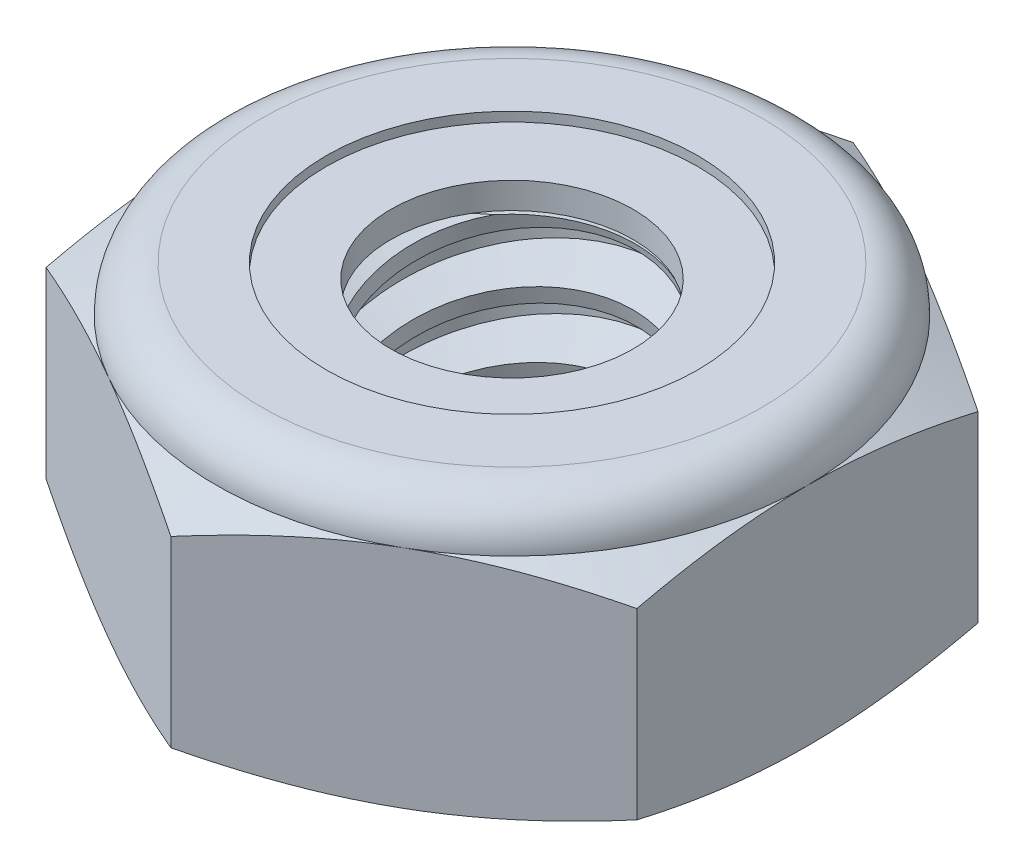
SolidWorks part; units mm, degrees
ref_plane "Front" through (0, 0, 0) normal (0, 0, 1) x (1, 0, 0)
ref_plane "Top" through (0, 0, 0) normal (0, 1, 0) x (1, 0, 0)
ref_plane "Right" through (0, 0, 0) normal (1, 0, 0) x (0, 0, -1)
sketch "Sketch1" plane through (0, 0, 0) normal (0, 1, 0) x (1, 0, 0)
  line L1 (0, 5.4993) -> (-4.7625, 2.7496)
  line L2 (-4.7625, 2.7496) -> (-4.7625, -2.7496)
  line L3 (-4.7625, -2.7496) -> (0, -5.4993)
  line L4 (0, -5.4993) -> (4.7625, -2.7496)
  line L5 (4.7625, -2.7496) -> (4.7625, 2.7496)
  line L6 (4.7625, 2.7496) -> (0, 5.4993)
  circle A0 centre (0, 0) radius 4.7625 construction
  dimension "Hex Flats" = 9.525
extrude "Extrude1" add sketch "Sketch1" along normal blind 4.3656
sketch "Sketch2" plane through (0, 0, 0) normal (1, 0, 0) x (0, 0, -1)
  line L0 (-2.413, 0) -> (-2.413, 4.3656) construction
  line L1 (0, 0) -> (2.413, 0)
  line L2 (0, 0) -> (0, 4.3656)
  line L3 (0, 4.3656) -> (2.413, 4.3656)
  line L4 (2.413, 0) -> (2.413, 4.3656)
  line L5 (-2.7496, 4.3656) -> (2.7496, 4.3656) construction
  line L7 (0, -2.413) -> (0, 0) construction
  dimension "Thread Dia" = 4.826
revolve "Revolve1" add sketch "Sketch2" angle 360 about L7
sketch "Sketch3" plane through (0, 0, 0) normal (1, 0, 0) x (0, 0, -1)
  line L0 (2.413, 4.3656) -> (-2.413, 4.3656) construction
  line L1 (-2.413, 4.3656) -> (-2.413, 3.3073) construction
  line L2 (-2.413, 3.3073) -> (2.413, 4.3656) construction
  line L3 (2.413, 4.3656) -> (2.4413, 4.2364) construction
  line L4 (2.4413, 4.2364) -> (2.6397, 3.3319)
  line L5 (2.6397, 3.3319) -> (2.0093, 3.5322)
  line L6 (2.0093, 3.5322) -> (1.9526, 3.7906)
  line L7 (1.9526, 3.7906) -> (2.4413, 4.2364)
  line L8 (1.981, 3.6614) -> (2.5405, 3.7841) construction
  line L9 (2.413, 4.3656) -> (2.413, 3.7562) construction
  line L10 (2.413, 3.7562) -> (-2.413, 2.6978) construction
  line L11 (-2.413, 2.6978) -> (-2.413, 3.3073) construction
  line L12 (-0.2497, 4.3656) -> (0.2497, 2.0884) construction
  line L13 (-2.413, 0) -> (-2.413, 4.3656) construction
  line L14 (0, 4.3656) -> (2.413, 4.3656) construction
  line L15 (2.413, 0) -> (2.413, 4.3656) construction
  point P13 (0, 3.227)
  dimension "D1" = 0.1323
  dimension "D2" = 0.2646
  dimension "Thread Pitch" = 1.0583
  dimension "D4" = 60
  dimension "D5" = 1.0583
revolve "Cut-Revolve1" cut sketch "Sketch3" angle 360 about L12
pattern_linear "LPattern1" count 4 spacing 1.0583 along (0, -1, 0) count 2 spacing 1.0583 along (0, 1, 0) of "Cut-Revolve1"
sketch "Sketch4" plane through (0, 0, 0) normal (1, 0, 0) x (0, 0, -1)
  line L0 (0, 4.3656) -> (2.413, 4.3656)
  line L1 (2.413, 4.3656) -> (1.9526, 4.151)
  line L2 (1.9526, 4.151) -> (1.9526, 0.2147)
  line L3 (1.9526, 0.2147) -> (2.413, 0)
  line L4 (2.413, 0) -> (0, 0)
  line L5 (0, 0) -> (0, 4.3656)
  line L6 (2.413, 0) -> (2.413, 4.3656) construction
  line L7 (0, 4.3656) -> (2.413, 4.3656) construction
  line L8 (0, 0) -> (2.413, 0) construction
  line L9 (0, 0) -> (0, 4.3656) construction
  line L10 (0, 4.3656) -> (0, 4.8736) construction
  dimension "D1" = 25
revolve "Cut-Revolve2" cut sketch "Sketch4" angle 360 about L10
combine bodies "Combine1" operation type subtract main body 112 bodies to subtract 111
sketch "Sketch5" plane through (0, 0, 0) normal (1, 0, 0) x (0, 0, -1)
  line L0 (0, 0) -> (4.7625, 0)
  line L1 (4.7625, 0) -> (5.4993, 0.3436)
  line L2 (5.4993, 0.3436) -> (5.4993, 3.2945)
  line L3 (5.4993, 3.2945) -> (4.7625, 3.638)
  line L4 (4.0349, 4.3656) -> (4.0349, 5.6356)
  line L5 (4.0349, 5.6356) -> (6.7693, 5.6356)
  line L6 (6.7693, 5.6356) -> (6.7693, -1.27)
  line L7 (6.7693, -1.27) -> (0, -1.27)
  line L8 (0, -1.27) -> (0, 0)
  line L9 (4.7625, 3.638) -> (4.7625, 0) construction
  line L10 (0, 0) -> (2.413, 0) construction
  line L13 (5.4993, 1.819) -> (6.7693, 1.819) construction
  line L14 (5.4993, 4.3656) -> (5.4993, 0) construction
  line L15 (0, 0) -> (0, 5.6356) construction
  line L20 (0, 5.6356) -> (4.0349, 5.6356) construction
  line L22 (0, 4.3656) -> (2.413, 4.3656) construction
  arc A0 (4.7625, 3.638) -> (4.0349, 4.3656) centre (4.0349, 3.638) ccw
  dimension "D1" = 25
  dimension "D2" = 1.27
  dimension "D3" = 4.3656
  dimension "D4" = 0.7276
revolve "Cut-Revolve3" cut sketch "Sketch5" angle 360 about L15
sketch "Sketch6" plane through (0, 0, 0) normal (1, 0, 0) x (0, 0, -1)
  line L0 (0, 3.638) -> (4.6101, 3.638)
  line L1 (4.0349, 4.2132) -> (2.9938, 4.2132)
  line L2 (0, 5.6356) -> (0, 3.638)
  line L3 (2.9938, 5.6356) -> (0, 5.6356)
  line L4 (0, 5.6356) -> (4.0349, 5.6356) construction
  line L5 (0, 0) -> (0, 5.6356) construction
  line L6 (0, 5.6356) -> (0, 44.323) construction
  line L7 (2.9938, 4.2132) -> (2.9938, 5.6356)
  line L8 (4.0349, 4.3656) -> (4.0349, 4.2132) construction
  line L9 (2.9938, 4.2132) -> (1.9526, 4.2132) construction
  line L10 (1.9526, 4.2132) -> (1.9526, 4.151) construction
  arc A0 (4.6101, 3.638) -> (4.0349, 4.2132) centre (4.0349, 3.638) ccw
  arc A1 (4.7625, 3.638) -> (4.0349, 4.3656) centre (4.0349, 3.638) ccw construction
  dimension "D1" = 0.1524
revolve "Cut-Revolve4" cut sketch "Sketch6" angle 360 about L6
sketch "Sketch7" plane through (0, 0, 0) normal (1, 0, 0) x (0, 0, -1)
  line L0 (1.9526, 3.7142) -> (4.528, 3.7142)
  line L1 (4.0349, 4.137) -> (1.9526, 4.137)
  line L2 (1.9526, 4.137) -> (1.9526, 3.7142)
  line L3 (1.9526, 3.7142) -> (0, 3.7142) construction
  line L4 (0, 3.7142) -> (0, 4.137) construction
  line L5 (0, 4.137) -> (1.9526, 4.137) construction
  line L6 (1.9526, 3.7142) -> (1.9526, 3.638) construction
  line L7 (0, 3.638) -> (4.6101, 3.638) construction
  line L8 (4.0349, 4.137) -> (4.0349, 4.2132) construction
  arc A0 (4.528, 3.7142) -> (4.0349, 4.137) centre (4.0349, 3.638) ccw
  arc A2 (4.6101, 3.638) -> (4.0349, 4.2132) centre (4.0349, 3.638) ccw construction
  dimension "D1" = 0.0762
revolve "Revolve2" add sketch "Sketch7" angle 360 about L4
equation "\"D1@Sketch3\"=\"Thread Pitch@Sketch3\"/8"
equation "\"D2@Sketch3\"=\"Thread Pitch@Sketch3\"/4"
equation "\"D5@Sketch3\"=\"Thread Pitch@Sketch3\""
equation "\"D4@LPattern1\"=\"Thread Pitch@Sketch3\""
equation "\"D3@LPattern1\"=\"Thread Pitch@Sketch3\""
equation "\"D1@LPattern1\"=\"Height@Extrude1\"/\"Thread Pitch@Sketch3\""
equation "\"D4@Sketch5\"=\"Height@Extrude1\"/6"
